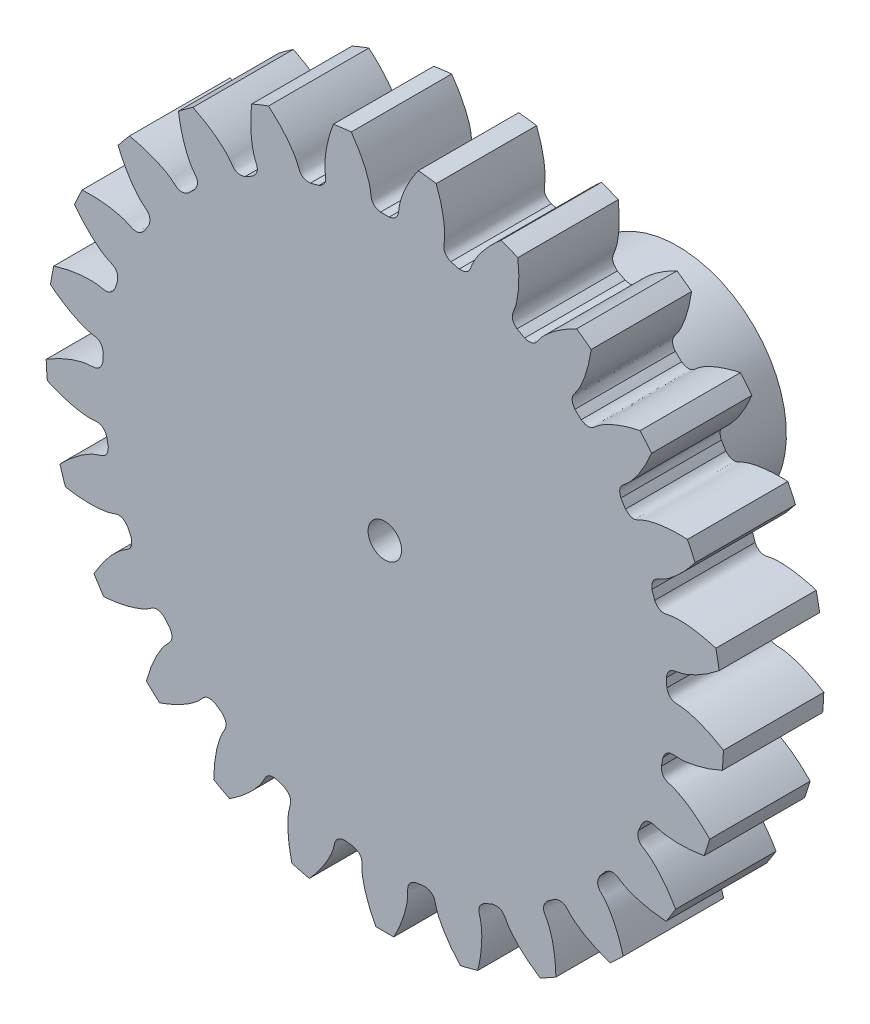
SolidWorks part; units mm, degrees
material "PET"
ref_plane "前视基准面" through (0, 0, 0) normal (0, 0, 1) x (1, 0, 0)
ref_plane "上视基准面" through (0, 0, 0) normal (0, 1, 0) x (1, 0, 0)
ref_plane "右视基准面" through (0, 0, 0) normal (1, 0, 0) x (0, 0, -1)
sketch "草图1" plane through (0, 0, 0) normal (0, 0, 1) x (1, 0, 0)
  circle A0 centre (0, 0) radius 20.25
extrude "凸台-拉伸1" add sketch "草图1" along normal blind 6
ref_axis "基准轴1" through (0, 0, -0.3) along (0, 0, 1)
sketch "草图2" plane through (0, 0, 0) normal (0, 0, 1) x (1, 0, 0)
  line L0 (0, 0) -> (0, 20.25) construction
  circle A0 centre (0, 0) radius 20.25 construction
  arc A1 (0.2581, 16.873) -> (-0.2581, 16.873) centre (0, 0) ccw
  arc A2 (4.8079, 22.9723) -> (-4.8079, 22.9723) centre (0, 0) ccw
  spline S0 degree 3 poles (0.2581, 16.873) (0.86, 17.0026) (0.8033, 17.3659) (0.8613, 17.7271) (0.8694, 17.7722) (0.8799, 17.824) (0.8929, 17.8825) (0.9087, 17.9475) (0.9276, 18.0191) (0.9499, 18.097) (0.9758, 18.1812) (1.0055, 18.2716) (1.0395, 18.368) (1.0778, 18.4703) (1.1207, 18.5784) (1.1685, 18.6921) (1.2215, 18.8112) (1.2798, 18.9357) (1.3437, 19.0652) (1.4135, 19.1998) (1.4892, 19.3391) (1.5713, 19.483) (1.6598, 19.6312) (1.755, 19.7837) (1.857, 19.9401) (1.9662, 20.1003) (2.0826, 20.264) (2.2065, 20.431) (2.3379, 20.601) (2.4772, 20.7739) (2.6245, 20.9494) (2.7798, 21.1272) (2.9434, 21.3071) (3.1155, 21.4888) (3.296, 21.672) (3.4853, 21.8565) (3.6833, 22.042) (3.8903, 22.2282) (4.1062, 22.4148) (4.41, 22.6669) (4.6462, 22.8511) (4.8079, 22.9723) knots 0 0 0 0 0.130741 0.135745 0.141658 0.148481 0.156214 0.164857 0.174409 0.184871 0.196243 0.208524 0.221715 0.235816 0.250827 0.266748 0.283578 0.301318 0.319968 0.339527 0.359996 0.381375 0.403664 0.426862 0.450971 0.475988 0.501916 0.528753 0.556501 0.585157 0.614724 0.6452 0.676587 0.708882 0.742088 0.776203 0.811228 0.847163 0.884008 0.921762 1 1 1 1
  spline S1 degree 3 poles (-0.2581, 16.873) (-0.86, 17.0026) (-0.8033, 17.3659) (-0.8613, 17.7271) (-0.8694, 17.7722) (-0.8799, 17.824) (-0.8929, 17.8825) (-0.9087, 17.9475) (-0.9276, 18.0191) (-0.9499, 18.097) (-0.9758, 18.1812) (-1.0055, 18.2716) (-1.0395, 18.368) (-1.0778, 18.4703) (-1.1207, 18.5784) (-1.1685, 18.6921) (-1.2215, 18.8112) (-1.2798, 18.9357) (-1.3437, 19.0652) (-1.4135, 19.1998) (-1.4892, 19.3391) (-1.5713, 19.483) (-1.6598, 19.6312) (-1.755, 19.7837) (-1.857, 19.9401) (-1.9662, 20.1003) (-2.0826, 20.264) (-2.2065, 20.431) (-2.3379, 20.601) (-2.4772, 20.7739) (-2.6245, 20.9494) (-2.7798, 21.1272) (-2.9434, 21.3071) (-3.1155, 21.4888) (-3.296, 21.672) (-3.4853, 21.8565) (-3.6833, 22.042) (-3.8903, 22.2282) (-4.1062, 22.4148) (-4.41, 22.6669) (-4.6462, 22.8511) (-4.8079, 22.9723) knots 0 0 0 0 0.130741 0.135745 0.141658 0.148481 0.156214 0.164857 0.174409 0.184871 0.196243 0.208524 0.221715 0.235816 0.250827 0.266748 0.283578 0.301318 0.319968 0.339527 0.359996 0.381375 0.403664 0.426862 0.450971 0.475988 0.501916 0.528753 0.556501 0.585157 0.614724 0.6452 0.676587 0.708882 0.742088 0.776203 0.811228 0.847163 0.884008 0.921762 1 1 1 1
extrude "切除-拉伸1" cut sketch "草图2" along normal through all
pattern_circular "阵列(圆周)1" count 25 every 14.4 about axis through (0, 0, -0.3) along (0, 0, 1) of "切除-拉伸1"
sketch "草图3" plane through (0, 0, 0) normal (0, 0, 1) x (1, 0, 0)
  circle A0 centre (0, 0) radius 18.75 construction
  dimension "Dn" = 37.5
sketch "草图4" plane through (0, 0, 0) normal (0, 0, -1) x (-1, 0, 0)
  line L0 (-1.6583, -2.5) -> (1.6583, -2.5)
  line L1 (6.6332, -10) -> (-6.6332, -10) construction
  arc A0 (1.6583, -2.5) -> (-1.6583, -2.5) centre (0, 0) ccw
  arc A1 (6.6332, -10) -> (-6.6332, -10) centre (0, 0) ccw construction
  circle A2 centre (0, 0) radius 6.5
  dimension "D1" = 6
  dimension "D2" = 24
  dimension "D4" = 13
  dimension "D3" = 2.5
  dimension "D5" = 10
extrude "凸台-拉伸2" add sketch "草图4" along normal blind 11.5
sketch "草图5" plane through (0, 0, 0) normal (0, 0, -1) x (-1, 0, 0)
  line L0 (-3.75, -5) -> (3.75, -5)
  arc A0 (3.75, -5) -> (-3.75, -5) centre (0, 0) ccw
  dimension "D1" = 12.5
  dimension "D2" = 5
extrude "凸台-拉伸3" add sketch "草图5" along normal blind 7.5
sketch "草图10" plane through (0, 0, -11.5) normal (0, 0, -1) x (-1, 0, 0)
  line L3 (4.1533, -5) -> (-4.1533, -5)
  arc A0 (4.1533, -5) -> (-4.1533, -5) centre (0, 0) ccw
  dimension "D1" = 13
  dimension "D2" = 5
extrude "切除-拉伸4" cut sketch "草图10" against normal blind 11.5 flip side to cut
sketch "草图6" plane through (0, 0, -11.5) normal (0, 0, -1) x (-1, 0, 0)
  line L3 (-1.6583, -2.5) -> (1.6583, -2.5)
  line L4 (-1.6583, -2.5) -> (1.6583, -2.5)
  arc A3 (1.6583, -2.5) -> (-1.6583, -2.5) centre (0, 0) ccw
  arc A4 (1.6583, -2.5) -> (-1.6583, -2.5) centre (0, 0) ccw
  dimension "D1" = 0
extrude "切除-拉伸2" cut sketch "草图6" against normal through all
sketch "草图7" plane through (0, -5, 0) normal (0, -1, 0) x (1, 0, 0)
  line L3 (4.1533, -11.5) -> (-4.1533, -11.5) construction
  circle A0 centre (0, -9) radius 1
  dimension "D1" = 2
  dimension "D2" = 2.5
extrude "切除-拉伸3" cut sketch "草图7" against normal blind 6
sketch "草图8" plane through (0, 0, 6) normal (0, 0, 1) x (1, 0, 0)
  line L1 (1.6583, -2.5) -> (-1.6583, -2.5) construction
  line L2 (1.6583, -2.5) -> (-1.6583, -2.5)
  circle A1 centre (0, 0) radius 6.25
  arc A2 (1.6583, -2.5) -> (-1.6583, -2.5) centre (0, 0) ccw construction
  arc A3 (1.6583, -2.5) -> (-1.6583, -2.5) centre (0, 0) ccw
  dimension "D1" = 12.5
extrude "凸台-拉伸4" add sketch "草图8" along normal blind 0.5
sketch "草图9" plane through (0, 0, 6.5) normal (0, 0, 1) x (1, 0, 0)
  circle A0 centre (0, 0) radius 1
  circle A1 centre (0, 0) radius 6.25
  circle A2 centre (0, 0) radius 6.25
  dimension "D2" = 2
  dimension "D1" = 0
extrude "凸台-拉伸5" add sketch "草图9" along normal blind 2
sketch "草图11" plane through (0, 0, 6.5) normal (0, 0, -1) x (-1, 0, 0)
  line L0 (1.6583, -2.5) -> (-1.6583, -2.5) construction
  line L1 (1.6583, -2.5) -> (-1.6583, -2.5)
  arc A0 (1.6583, -2.5) -> (-1.6583, -2.5) centre (0, 0) ccw construction
  arc A1 (1.6583, -2.5) -> (-1.6583, -2.5) centre (0, 0) ccw
  circle A2 centre (0, 0) radius 1 construction
  circle A3 centre (0, 0) radius 1
extrude "凸台-拉伸6" add sketch "草图11" along normal blind 8.5
sketch "草图12" plane through (0, 0, 8.5) normal (0, 0, 1) x (1, 0, 0)
  circle A0 centre (0, 0) radius 6.25 construction
  circle A1 centre (0, 0) radius 6.25
extrude "切除-拉伸5" cut sketch "草图12" against normal blind 2.5
